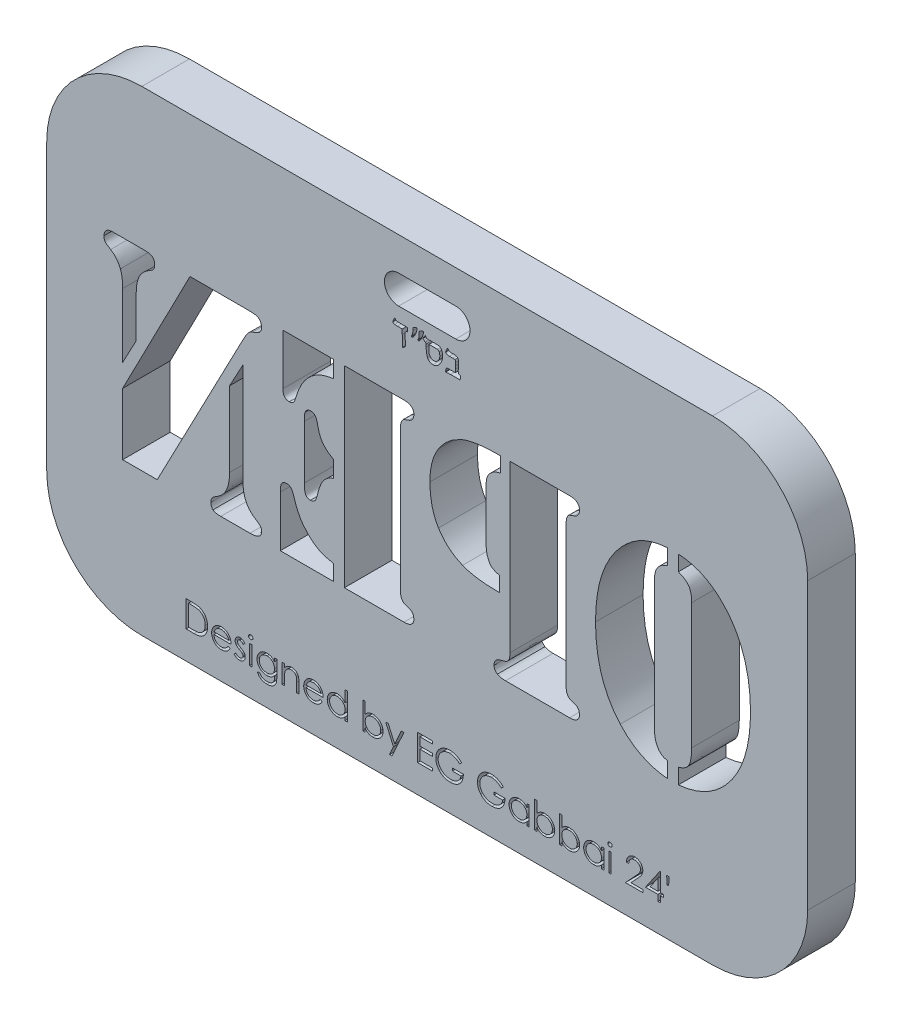
SolidWorks part; units mm, degrees
ref_plane "Front Plane" through (0, 0, 0) normal (0, 0, 1) x (1, 0, 0)
ref_plane "Top Plane" through (0, 0, 0) normal (0, 1, 0) x (1, 0, 0)
ref_plane "Right Plane" through (0, 0, 0) normal (1, 0, 0) x (0, 0, -1)
sketch "Sketch1" plane through (0, 0, 0) normal (0, 0, 1) x (1, 0, 0)
  line L1 (-88.9, 63.5) -> (-12.7, 63.5)
  line L2 (-101.6, 50.8) -> (-101.6, 12.7)
  line L3 (-88.9, 0) -> (-12.7, 0)
  line L4 (0, 50.8) -> (0, 12.7)
  arc A0 (-12.7, 0) -> (0, 12.7) centre (-12.7, 12.7) ccw
  arc A1 (-101.6, 12.7) -> (-88.9, 0) centre (-88.9, 12.7) ccw
  arc A2 (-12.7, 63.5) -> (0, 50.8) centre (-12.7, 50.8) cw
  arc A3 (-88.9, 63.5) -> (-101.6, 50.8) centre (-88.9, 50.8) ccw
  point P7 (0, 0)
  point P10 (-101.6, 0)
  point P13 (0, 63.5)
  point P16 (-101.6, 63.5)
  dimension "D3" = 12.7
  dimension "D4" = 12.7
  dimension "D5" = 12.7
  dimension "D6" = 12.7
  dimension "D1" = 101.6
  dimension "D2" = 63.5
extrude "Boss-Extrude1" add sketch "Sketch1" along normal blind 6.35
sketch "Sketch2" plane through (0, 0, 6.35) normal (0, 0, 1) x (1, 0, 0)
  line L3 (-101.6, 19.05) -> (0, 19.05) construction
  line L5 (-88.9, 0) -> (-12.7, 0) construction
  text T0 "Open" font "Stencil" height in points 100
  point P3 (0, 0)
  point P6 (0, 0)
  point P7 (0, 0)
  point P8 (0, 0)
  dimension "D1" = 19.05
extrude "Cut-Extrude1" cut sketch "Sketch2" against normal blind 6.35
sketch "Sketch3" plane through (0, 0, 6.35) normal (0, 0, 1) x (1, 0, 0)
  line L0 (-54.61, 57.15) -> (-46.99, 57.15) construction
  line L1 (-54.61, 59.055) -> (-46.99, 59.055)
  line L2 (-54.61, 55.245) -> (-46.99, 55.245)
  line L3 (-101.6, 50.8) -> (-101.6, 12.7) construction
  line L6 (-12.7, 63.5) -> (-88.9, 63.5) construction
  arc A0 (-54.61, 59.055) -> (-54.61, 55.245) centre (-54.61, 57.15) ccw
  arc A1 (-46.99, 55.245) -> (-46.99, 59.055) centre (-46.99, 57.15) ccw
  point P2 (-50.8, 57.15)
  point P16 (-50.8, 63.5)
  dimension "D1" = 50.8
  dimension "D2" = 6.35
  dimension "D3" = 3.81
  dimension "D4" = 7.62
extrude "Cut-Extrude2" cut sketch "Sketch3" against normal blind 6.35
sketch "Sketch4" plane through (0, 0, 6.35) normal (0, 0, 1) x (1, 0, 0)
  line L0 (-97.8803, 3.7197) -> (-3.7197, 3.7197) construction
  line L1 (-101.6, 50.8) -> (0, 50.8) construction
  arc A0 (-101.6, 12.7) -> (-88.9, 0) centre (-88.9, 12.7) ccw construction
  arc A1 (-12.7, 0) -> (0, 12.7) centre (-12.7, 12.7) ccw construction
  text T0 "בס״ד" font "Narkisim" height 3.5
  text T1 "Designed by EG Gabbai 24'"
  point P15 (-50.8, 50.8)
extrude "Cut-Extrude3" cut sketch "Sketch4" against normal blind 2.54
